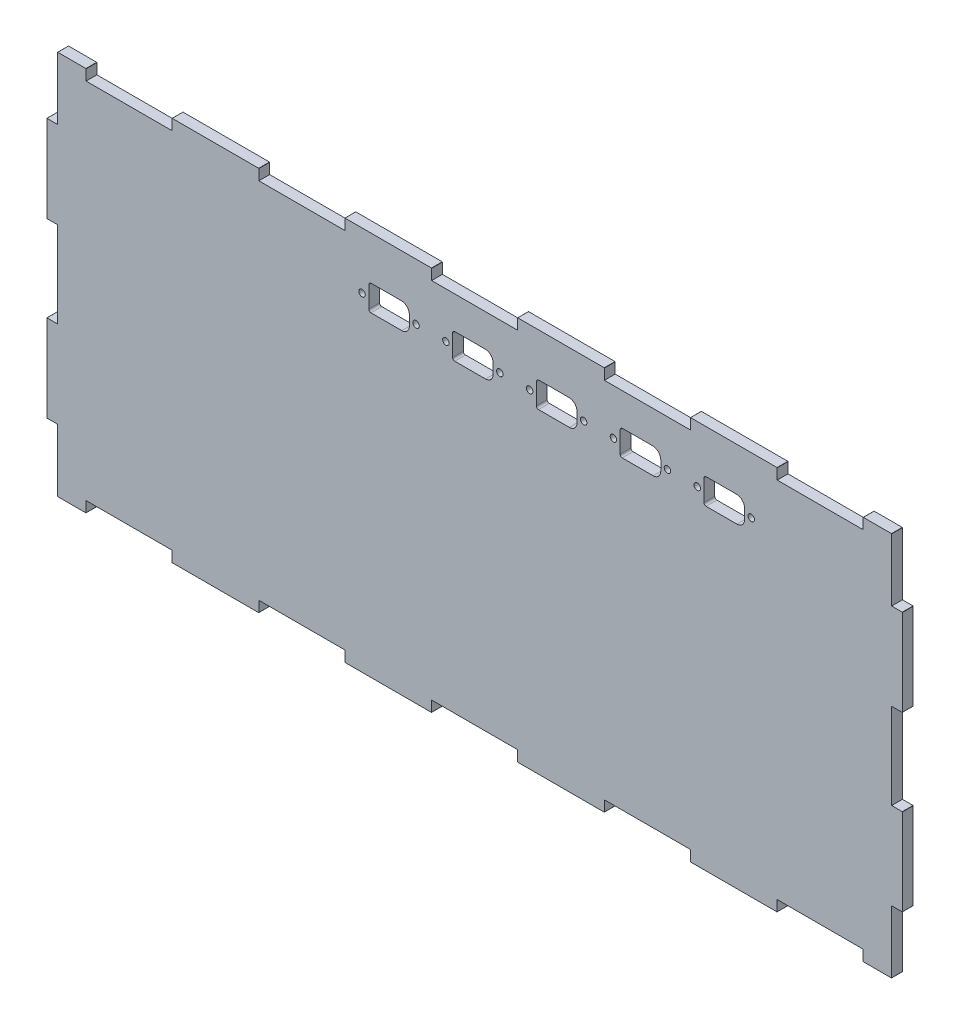
SolidWorks part; units mm, degrees
ref_plane "Front Plane" through (0, 0, 0) normal (0, 0, 1) x (1, 0, 0)
ref_plane "Top Plane" through (0, 0, 0) normal (0, 1, 0) x (1, 0, 0)
ref_plane "Right Plane" through (0, 0, 0) normal (1, 0, 0) x (0, 0, -1)
sketch "Model" plane through (0, 0, 0) normal (0, 0, 1) x (1, 0, 0)
  line L0 (-179.94, -89.08) -> (-179.93, -89.07)
  line L1 (-179.93, -89.07) -> (-179.92, -89.05)
  line L2 (-179.92, -89.05) -> (-179.91, -89.04)
  line L3 (-179.91, -89.04) -> (-179.9, -89.02)
  line L4 (-179.9, -89.02) -> (-179.9, -84.1)
  line L5 (-179.9, -84.1) -> (-140.1, -84.1)
  line L6 (-140.1, -84.1) -> (-140.1, -89.02)
  line L7 (-140.1, -89.02) -> (-140.08, -89.06)
  line L8 (-140.08, -89.06) -> (-140.07, -89.07)
  line L9 (-140.07, -89.07) -> (-140.05, -89.08)
  line L10 (-140.05, -89.08) -> (-140.04, -89.09)
  line L11 (-140.04, -89.09) -> (-140.02, -89.1)
  line L12 (-140.02, -89.1) -> (-99.98, -89.1)
  line L13 (-99.98, -89.1) -> (-99.94, -89.08)
  line L14 (-99.94, -89.08) -> (-99.93, -89.07)
  line L15 (-99.93, -89.07) -> (-99.92, -89.05)
  line L16 (-99.92, -89.05) -> (-99.91, -89.04)
  line L17 (-99.91, -89.04) -> (-99.9, -89.02)
  line L18 (-99.9, -89.02) -> (-99.9, -84.1)
  line L19 (-99.9, -84.1) -> (-60.1, -84.1)
  line L20 (-60.1, -84.1) -> (-60.1, -89.02)
  line L21 (-60.1, -89.02) -> (-60.08, -89.06)
  line L22 (-60.08, -89.06) -> (-60.07, -89.07)
  line L23 (-60.07, -89.07) -> (-60.05, -89.08)
  line L24 (-60.05, -89.08) -> (-60.04, -89.09)
  line L25 (-60.04, -89.09) -> (-60.02, -89.1)
  line L26 (-60.02, -89.1) -> (-19.98, -89.1)
  line L27 (-19.98, -89.1) -> (-19.94, -89.08)
  line L28 (-19.94, -89.08) -> (-19.93, -89.07)
  line L29 (-19.93, -89.07) -> (-19.92, -89.05)
  line L30 (-19.92, -89.05) -> (-19.91, -89.04)
  line L31 (-19.91, -89.04) -> (-19.9, -89.02)
  line L32 (-19.9, -89.02) -> (-19.9, -84.1)
  line L33 (-19.9, -84.1) -> (19.9, -84.1)
  line L34 (19.9, -84.1) -> (19.9, -89.02)
  line L35 (19.9, -89.02) -> (19.92, -89.06)
  line L36 (19.92, -89.06) -> (19.93, -89.07)
  line L37 (19.93, -89.07) -> (19.95, -89.08)
  line L38 (19.95, -89.08) -> (19.96, -89.09)
  line L39 (19.96, -89.09) -> (19.98, -89.1)
  line L40 (19.98, -89.1) -> (60.02, -89.1)
  line L41 (60.02, -89.1) -> (60.06, -89.08)
  line L42 (60.06, -89.08) -> (60.07, -89.07)
  line L43 (60.07, -89.07) -> (60.08, -89.05)
  line L44 (60.08, -89.05) -> (60.09, -89.04)
  line L45 (60.09, -89.04) -> (60.1, -89.02)
  line L46 (60.1, -89.02) -> (60.1, -84.1)
  line L47 (60.1, -84.1) -> (99.9, -84.1)
  line L48 (99.9, -84.1) -> (99.9, -89.02)
  line L49 (99.9, -89.02) -> (99.92, -89.06)
  line L50 (99.92, -89.06) -> (99.93, -89.07)
  line L51 (99.93, -89.07) -> (99.95, -89.08)
  line L52 (99.95, -89.08) -> (99.96, -89.09)
  line L53 (99.96, -89.09) -> (99.98, -89.1)
  line L54 (99.98, -89.1) -> (140.02, -89.1)
  line L55 (140.02, -89.1) -> (140.06, -89.08)
  line L56 (140.06, -89.08) -> (140.07, -89.07)
  line L57 (140.07, -89.07) -> (140.08, -89.05)
  line L58 (140.08, -89.05) -> (140.09, -89.04)
  line L59 (140.09, -89.04) -> (140.1, -89.02)
  line L60 (140.1, -89.02) -> (140.1, -84.1)
  line L61 (140.1, -84.1) -> (179.9, -84.1)
  line L62 (179.9, -84.1) -> (179.9, -89.02)
  line L63 (179.9, -89.02) -> (179.92, -89.06)
  line L64 (179.92, -89.06) -> (179.93, -89.07)
  line L65 (179.93, -89.07) -> (179.95, -89.08)
  line L66 (179.95, -89.08) -> (179.96, -89.09)
  line L67 (179.96, -89.09) -> (179.98, -89.1)
  line L68 (179.98, -89.1) -> (193.02, -89.1)
  line L69 (193.02, -89.1) -> (193.06, -89.08)
  line L70 (193.06, -89.08) -> (193.07, -89.07)
  line L71 (193.07, -89.07) -> (193.08, -89.05)
  line L72 (193.08, -89.05) -> (193.09, -89.04)
  line L73 (193.09, -89.04) -> (193.1, -89.02)
  line L74 (193.1, -89.02) -> (193.1, -60.1)
  line L75 (193.1, -60.1) -> (198.02, -60.1)
  line L76 (198.02, -60.1) -> (198.06, -60.08)
  line L77 (198.06, -60.08) -> (198.07, -60.07)
  line L78 (198.07, -60.07) -> (198.08, -60.05)
  line L79 (198.08, -60.05) -> (198.09, -60.04)
  line L80 (198.09, -60.04) -> (198.1, -60.02)
  line L81 (198.1, -60.02) -> (198.1, -19.98)
  line L82 (198.1, -19.98) -> (198.08, -19.94)
  line L83 (198.08, -19.94) -> (198.07, -19.93)
  line L84 (198.07, -19.93) -> (198.05, -19.92)
  line L85 (198.05, -19.92) -> (198.04, -19.91)
  line L86 (198.04, -19.91) -> (198.02, -19.9)
  line L87 (198.02, -19.9) -> (193.1, -19.9)
  line L88 (193.1, -19.9) -> (193.1, 19.9)
  line L89 (193.1, 19.9) -> (198.02, 19.9)
  line L90 (198.02, 19.9) -> (198.06, 19.92)
  line L91 (198.06, 19.92) -> (198.07, 19.93)
  line L92 (198.07, 19.93) -> (198.08, 19.95)
  line L93 (198.08, 19.95) -> (198.09, 19.96)
  line L94 (198.09, 19.96) -> (198.1, 19.98)
  line L95 (198.1, 19.98) -> (198.1, 60.02)
  line L96 (198.1, 60.02) -> (198.08, 60.06)
  line L97 (198.08, 60.06) -> (198.07, 60.07)
  line L98 (198.07, 60.07) -> (198.05, 60.08)
  line L99 (198.05, 60.08) -> (198.04, 60.09)
  line L100 (198.04, 60.09) -> (198.02, 60.1)
  line L101 (198.02, 60.1) -> (193.1, 60.1)
  line L102 (193.1, 60.1) -> (193.1, 89.02)
  line L103 (193.1, 89.02) -> (193.08, 89.06)
  line L104 (193.08, 89.06) -> (193.07, 89.07)
  line L105 (193.07, 89.07) -> (193.05, 89.08)
  line L106 (193.05, 89.08) -> (193.04, 89.09)
  line L107 (193.04, 89.09) -> (193.02, 89.1)
  line L108 (193.02, 89.1) -> (179.98, 89.1)
  line L109 (179.98, 89.1) -> (179.94, 89.08)
  line L110 (179.94, 89.08) -> (179.93, 89.07)
  line L111 (179.93, 89.07) -> (179.92, 89.05)
  line L112 (179.92, 89.05) -> (179.91, 89.04)
  line L113 (179.91, 89.04) -> (179.9, 89.02)
  line L114 (179.9, 89.02) -> (179.9, 84.1)
  line L115 (179.9, 84.1) -> (140.1, 84.1)
  line L116 (140.1, 84.1) -> (140.1, 89.02)
  line L117 (140.1, 89.02) -> (140.08, 89.06)
  line L118 (140.08, 89.06) -> (140.07, 89.07)
  line L119 (140.07, 89.07) -> (140.05, 89.08)
  line L120 (140.05, 89.08) -> (140.04, 89.09)
  line L121 (140.04, 89.09) -> (140.02, 89.1)
  line L122 (140.02, 89.1) -> (99.98, 89.1)
  line L123 (99.98, 89.1) -> (99.94, 89.08)
  line L124 (99.94, 89.08) -> (99.93, 89.07)
  line L125 (99.93, 89.07) -> (99.92, 89.05)
  line L126 (99.92, 89.05) -> (99.91, 89.04)
  line L127 (99.91, 89.04) -> (99.9, 89.02)
  line L128 (99.9, 89.02) -> (99.9, 84.1)
  line L129 (99.9, 84.1) -> (60.1, 84.1)
  line L130 (60.1, 84.1) -> (60.1, 89.02)
  line L131 (60.1, 89.02) -> (60.08, 89.06)
  line L132 (60.08, 89.06) -> (60.07, 89.07)
  line L133 (60.07, 89.07) -> (60.05, 89.08)
  line L134 (60.05, 89.08) -> (60.04, 89.09)
  line L135 (60.04, 89.09) -> (60.02, 89.1)
  line L136 (60.02, 89.1) -> (19.98, 89.1)
  line L137 (19.98, 89.1) -> (19.94, 89.08)
  line L138 (19.94, 89.08) -> (19.93, 89.07)
  line L139 (19.93, 89.07) -> (19.92, 89.05)
  line L140 (19.92, 89.05) -> (19.91, 89.04)
  line L141 (19.91, 89.04) -> (19.9, 89.02)
  line L142 (19.9, 89.02) -> (19.9, 84.1)
  line L143 (19.9, 84.1) -> (-19.9, 84.1)
  line L144 (-19.9, 84.1) -> (-19.9, 89.02)
  line L145 (-19.9, 89.02) -> (-19.92, 89.06)
  line L146 (-19.92, 89.06) -> (-19.93, 89.07)
  line L147 (-19.93, 89.07) -> (-19.95, 89.08)
  line L148 (-19.95, 89.08) -> (-19.96, 89.09)
  line L149 (-19.96, 89.09) -> (-19.98, 89.1)
  line L150 (-19.98, 89.1) -> (-60.02, 89.1)
  line L151 (-60.02, 89.1) -> (-60.06, 89.08)
  line L152 (-60.06, 89.08) -> (-60.07, 89.07)
  line L153 (-60.07, 89.07) -> (-60.08, 89.05)
  line L154 (-60.08, 89.05) -> (-60.09, 89.04)
  line L155 (-60.09, 89.04) -> (-60.1, 89.02)
  line L156 (-60.1, 89.02) -> (-60.1, 84.1)
  line L157 (-60.1, 84.1) -> (-99.9, 84.1)
  line L158 (-99.9, 84.1) -> (-99.9, 89.02)
  line L159 (-99.9, 89.02) -> (-99.92, 89.06)
  line L160 (-99.92, 89.06) -> (-99.93, 89.07)
  line L161 (-99.93, 89.07) -> (-99.95, 89.08)
  line L162 (-99.95, 89.08) -> (-99.96, 89.09)
  line L163 (-99.96, 89.09) -> (-99.98, 89.1)
  line L164 (-99.98, 89.1) -> (-140.02, 89.1)
  line L165 (-140.02, 89.1) -> (-140.06, 89.08)
  line L166 (-140.06, 89.08) -> (-140.07, 89.07)
  line L167 (-140.07, 89.07) -> (-140.08, 89.05)
  line L168 (-140.08, 89.05) -> (-140.09, 89.04)
  line L169 (-140.09, 89.04) -> (-140.1, 89.02)
  line L170 (-140.1, 89.02) -> (-140.1, 84.1)
  line L171 (-140.1, 84.1) -> (-179.9, 84.1)
  line L172 (-179.9, 84.1) -> (-179.9, 89.02)
  line L173 (-179.9, 89.02) -> (-179.92, 89.06)
  line L174 (-179.92, 89.06) -> (-179.93, 89.07)
  line L175 (-179.93, 89.07) -> (-179.95, 89.08)
  line L176 (-179.95, 89.08) -> (-179.96, 89.09)
  line L177 (-179.96, 89.09) -> (-179.98, 89.1)
  line L178 (-179.98, 89.1) -> (-193.02, 89.1)
  line L179 (-193.02, 89.1) -> (-193.06, 89.08)
  line L180 (-193.06, 89.08) -> (-193.07, 89.07)
  line L181 (-193.07, 89.07) -> (-193.08, 89.05)
  line L182 (-193.08, 89.05) -> (-193.09, 89.04)
  line L183 (-193.09, 89.04) -> (-193.1, 89.02)
  line L184 (-193.1, 89.02) -> (-193.1, 60.1)
  line L185 (-193.1, 60.1) -> (-198.02, 60.1)
  line L186 (-198.02, 60.1) -> (-198.06, 60.08)
  line L187 (-198.06, 60.08) -> (-198.07, 60.07)
  line L188 (-198.07, 60.07) -> (-198.08, 60.05)
  line L189 (-198.08, 60.05) -> (-198.09, 60.04)
  line L190 (-198.09, 60.04) -> (-198.1, 60.02)
  line L191 (-198.1, 60.02) -> (-198.1, 19.98)
  line L192 (-198.1, 19.98) -> (-198.08, 19.94)
  line L193 (-198.08, 19.94) -> (-198.07, 19.93)
  line L194 (-198.07, 19.93) -> (-198.05, 19.92)
  line L195 (-198.05, 19.92) -> (-198.04, 19.91)
  line L196 (-198.04, 19.91) -> (-198.02, 19.9)
  line L197 (-198.02, 19.9) -> (-193.1, 19.9)
  line L198 (-193.1, 19.9) -> (-193.1, -19.9)
  line L199 (-193.1, -19.9) -> (-198.02, -19.9)
  line L200 (-198.02, -19.9) -> (-198.06, -19.92)
  line L201 (-198.06, -19.92) -> (-198.07, -19.93)
  line L202 (-198.07, -19.93) -> (-198.08, -19.95)
  line L203 (-198.08, -19.95) -> (-198.09, -19.96)
  line L204 (-198.09, -19.96) -> (-198.1, -19.98)
  line L205 (-198.1, -19.98) -> (-198.1, -60.02)
  line L206 (-198.1, -60.02) -> (-198.08, -60.06)
  line L207 (-198.08, -60.06) -> (-198.07, -60.07)
  line L208 (-198.07, -60.07) -> (-198.05, -60.08)
  line L209 (-198.05, -60.08) -> (-198.04, -60.09)
  line L210 (-198.04, -60.09) -> (-198.02, -60.1)
  line L211 (-198.02, -60.1) -> (-193.1, -60.1)
  line L212 (-193.1, -60.1) -> (-193.1, -89.02)
  line L213 (-193.1, -89.02) -> (-193.08, -89.06)
  line L214 (-193.08, -89.06) -> (-193.07, -89.07)
  line L215 (-193.07, -89.07) -> (-193.05, -89.08)
  line L216 (-193.05, -89.08) -> (-193.04, -89.09)
  line L217 (-193.04, -89.09) -> (-193.02, -89.1)
  line L218 (-193.02, -89.1) -> (-179.98, -89.1)
  line L219 (-179.98, -89.1) -> (-179.94, -89.08)
extrude "Boss-Extrude1" add sketch "Model" along normal blind 5
sketch "Sketch2" plane through (0, 0, 5) normal (0, 0, 1) x (1, 0, 0)
  line L0 (-30.2088, 62.97) -> (-10.2088, 62.97) construction
  line L1 (-33.7338, 57.12) -> (-48.0088, 57.12)
  line L2 (-47.8088, 69.02) -> (-33.9338, 69.02)
  line L3 (-49.0088, 58.12) -> (-49.0088, 67.82)
  line L4 (-30.2088, 60.645) -> (-30.2088, 65.295)
  line L5 (5.0662, 57.12) -> (-9.2088, 57.12)
  line L6 (-9.0088, 69.02) -> (4.8662, 69.02)
  line L7 (-10.2088, 58.12) -> (-10.2088, 67.82)
  line L8 (8.5912, 60.645) -> (8.5912, 65.295)
  line L9 (43.8662, 57.12) -> (29.5912, 57.12)
  line L10 (29.7912, 69.02) -> (43.6662, 69.02)
  line L11 (28.5912, 58.12) -> (28.5912, 67.82)
  line L12 (47.3912, 60.645) -> (47.3912, 65.295)
  line L13 (82.6662, 57.12) -> (68.3912, 57.12)
  line L14 (68.5912, 69.02) -> (82.4662, 69.02)
  line L15 (67.3912, 58.12) -> (67.3912, 67.82)
  line L16 (86.1912, 60.645) -> (86.1912, 65.295)
  line L17 (8.5912, 62.97) -> (28.5912, 62.97) construction
  line L18 (47.3912, 62.97) -> (67.3912, 62.97) construction
  line L19 (121.4662, 57.12) -> (107.1912, 57.12)
  line L20 (107.3912, 69.02) -> (121.2662, 69.02)
  line L21 (106.1912, 58.12) -> (106.1912, 67.82)
  line L22 (124.9912, 60.645) -> (124.9912, 65.295)
  line L23 (86.1912, 62.97) -> (106.1912, 62.97) construction
  line L24 (-52.1088, 62.97) -> (-49.0088, 62.97) construction
  line L25 (-13.3088, 62.97) -> (-10.2088, 62.97) construction
  line L26 (25.4912, 62.97) -> (28.5912, 62.97) construction
  line L27 (64.2912, 62.97) -> (67.3912, 62.97) construction
  line L28 (103.0912, 62.97) -> (106.1912, 62.97) construction
  line L29 (128.0912, 62.97) -> (193.1, 62.97) construction
  line L30 (193.1, 62.97) -> (193.1, 89.02) construction
  arc A0 (-30.2088, 60.645) -> (-33.7338, 57.12) centre (-33.7338, 60.645) cw
  arc A1 (-30.2088, 65.295) -> (-33.9338, 69.02) centre (-33.9338, 65.295) ccw
  arc A2 (-48.0088, 57.12) -> (-49.0088, 58.12) centre (-48.0088, 58.12) cw
  arc A3 (-49.0088, 67.82) -> (-47.8088, 69.02) centre (-47.8088, 67.82) cw
  arc A4 (8.5912, 60.645) -> (5.0662, 57.12) centre (5.0662, 60.645) cw
  arc A5 (8.5912, 65.295) -> (4.8662, 69.02) centre (4.8662, 65.295) ccw
  arc A6 (-9.2088, 57.12) -> (-10.2088, 58.12) centre (-9.2088, 58.12) cw
  arc A7 (-10.2088, 67.82) -> (-9.0088, 69.02) centre (-9.0088, 67.82) cw
  arc A8 (47.3912, 60.645) -> (43.8662, 57.12) centre (43.8662, 60.645) cw
  arc A9 (47.3912, 65.295) -> (43.6662, 69.02) centre (43.6662, 65.295) ccw
  arc A10 (29.5912, 57.12) -> (28.5912, 58.12) centre (29.5912, 58.12) cw
  arc A11 (28.5912, 67.82) -> (29.7912, 69.02) centre (29.7912, 67.82) cw
  arc A12 (86.1912, 60.645) -> (82.6662, 57.12) centre (82.6662, 60.645) cw
  arc A13 (86.1912, 65.295) -> (82.4662, 69.02) centre (82.4662, 65.295) ccw
  arc A14 (68.3912, 57.12) -> (67.3912, 58.12) centre (68.3912, 58.12) cw
  arc A15 (67.3912, 67.82) -> (68.5912, 69.02) centre (68.5912, 67.82) cw
  arc A16 (124.9912, 60.645) -> (121.4662, 57.12) centre (121.4662, 60.645) cw
  arc A17 (124.9912, 65.295) -> (121.2662, 69.02) centre (121.2662, 65.295) ccw
  arc A18 (107.1912, 57.12) -> (106.1912, 58.12) centre (107.1912, 58.12) cw
  arc A19 (106.1912, 67.82) -> (107.3912, 69.02) centre (107.3912, 67.82) cw
  circle A20 centre (-52.1088, 62.97) radius 1.5
  circle A21 centre (-27.1088, 62.97) radius 1.5
  circle A22 centre (-13.3088, 62.97) radius 1.5
  circle A23 centre (11.6912, 62.97) radius 1.5
  circle A24 centre (25.4912, 62.97) radius 1.5
  circle A25 centre (50.4912, 62.97) radius 1.5
  circle A26 centre (64.2912, 62.97) radius 1.5
  circle A27 centre (89.2912, 62.97) radius 1.5
  circle A28 centre (103.0912, 62.97) radius 1.5
  circle A29 centre (128.0912, 62.97) radius 1.5
  dimension "D5" = 3
  dimension "D6" = 3
  dimension "D1" = 20
  dimension "D2" = 20
  dimension "D3" = 20
  dimension "D4" = 20
  dimension "D7" = 25
extrude "Cut-Extrude1" cut sketch "Sketch2" against normal through all
